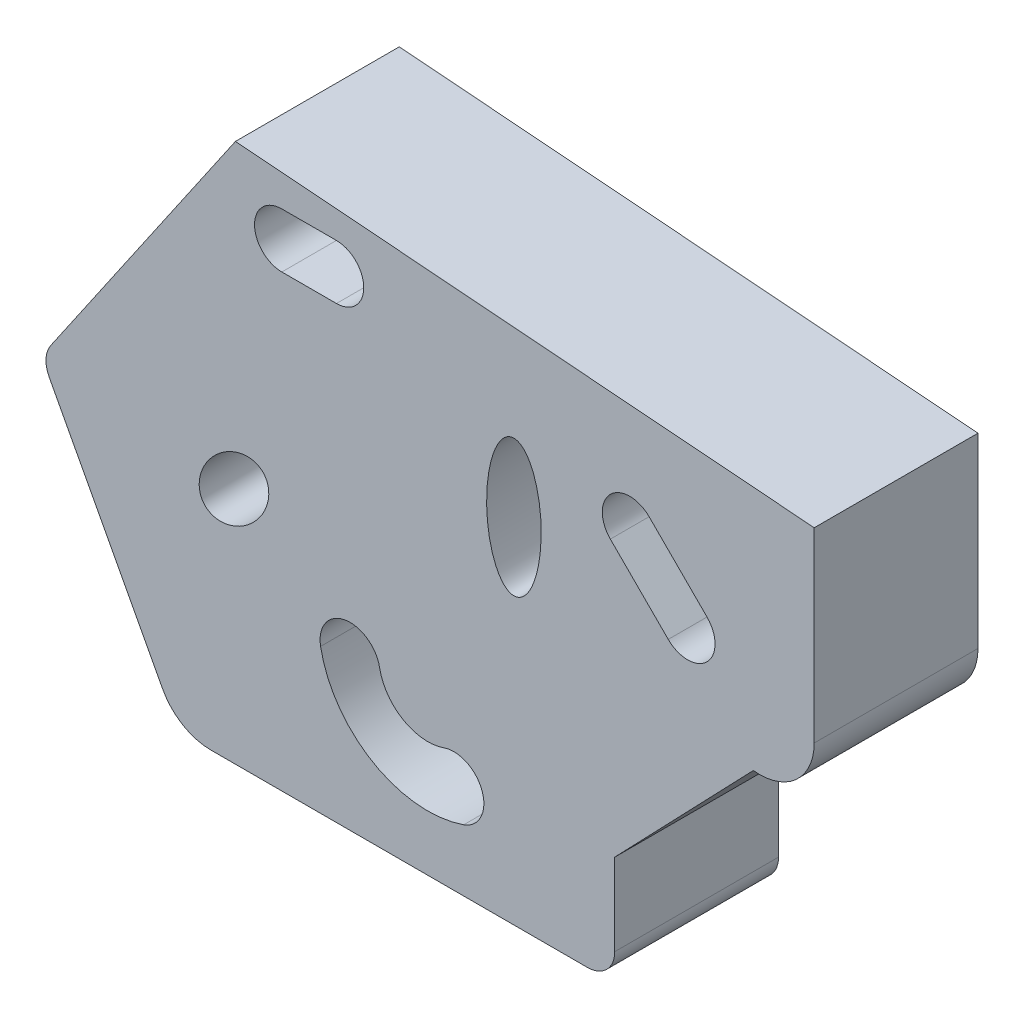
SolidWorks part; units mm, degrees
ref_plane "Front Plane" through (0, 0, 0) normal (0, 0, 1) x (1, 0, 0)
ref_plane "Top Plane" through (0, 0, 0) normal (0, 1, 0) x (1, 0, 0)
ref_plane "Right Plane" through (0, 0, 0) normal (1, 0, 0) x (0, 0, -1)
sketch "草图3" plane through (0, 0, 0) normal (0, 0, 1) x (1, 0, 0)
  line L0 (0, 0) -> (212, -16.5598)
  line L1 (212, -16.5598) -> (212, -84.8498)
  line L2 (189.6995, -104.717) -> (138.9354, -157.5794)
  line L3 (138.9354, -157.5794) -> (138.9354, -187.5794)
  line L4 (128.9354, -197.5794) -> (-9.0474, -197.5794)
  line L5 (-26.7064, -186.9688) -> (-68.2217, -108.8898)
  line L6 (-67.6368, -98.5358) -> (0, 0)
  line L7 (102, -7.9674) -> (102, -197.5794) construction
  line L8 (17, -22.9206) -> (37, -22.9206) construction
  line L9 (17, -12.9206) -> (37, -12.9206)
  line L10 (17, -32.9206) -> (37, -32.9206)
  line L11 (102, -7.9674) -> (-44.1655, -154.1329) construction
  line L12 (102, -7.9674) -> (194.1329, -100.1003) construction
  line L13 (144.4264, -50.3938) -> (165.6396, -71.6071) construction
  line L14 (151.5275, -43.2927) -> (172.7407, -64.5059)
  line L15 (137.3253, -57.495) -> (158.5385, -78.7082)
  arc A0 (212, -84.8498) -> (189.6995, -104.717) centre (192, -84.8498) cw
  arc A1 (128.9354, -197.5794) -> (138.9354, -187.5794) centre (128.9354, -187.5794) ccw
  arc A2 (-9.0474, -197.5794) -> (-26.7064, -186.9688) centre (-9.0474, -177.5794) cw
  arc A3 (-68.2217, -108.8898) -> (-67.6368, -98.5358) centre (-59.3922, -104.1951) cw
  arc A4 (17, -12.9206) -> (17, -32.9206) centre (17, -22.9206) ccw
  arc A5 (37, -32.9206) -> (37, -12.9206) centre (37, -22.9206) ccw
  arc A6 (151.5275, -43.2927) -> (137.3253, -57.495) centre (144.4264, -50.3938) ccw
  arc A7 (158.5385, -78.7082) -> (172.7407, -64.5059) centre (165.6396, -71.6071) ccw
  arc A8 (42, -142.5794) -> (80, -164.5794) centre (70.4571, -137.2444) ccw construction
  arc A13 (31.1884, -144.6063) -> (83.6256, -174.9647) centre (70.4571, -137.2444) ccw
  arc A14 (52.8116, -140.5525) -> (76.3744, -154.1941) centre (70.4571, -137.2444) ccw
  arc A15 (52.8116, -140.5525) -> (31.1884, -144.6063) centre (42, -142.5794) ccw
  arc A16 (83.6256, -174.9647) -> (76.3744, -154.1941) centre (80, -164.5794) ccw
  ellipse E0 centre (-0.5305, -110.4979) end of major axis (-11.1371, -121.1045) minor radius 10
  ellipse E1 centre (102, -68.1502) end of major axis (102, -43.1502) minor radius 10
  point P16 (27, -22.9206)
  point P21 (-21.0646, -197.5794)
  point P42 (155.033, -61.0004)
  point P50 (55.9507, -162.301)
  point P57 (-121.0684, 9.2337)
  point P58 (42.0768, -128.1805)
  point P59 (-138.5387, -38.1052)
  dimension "D4" = 20
  dimension "D7" = 20
  dimension "D11" = 20
  dimension "D12" = 10
  dimension "D16" = 118
  dimension "D18" = 20
  dimension "D35" = 11
  dimension "D1" = 102
  dimension "D2" = 110
  dimension "D3" = 68.29
  dimension "D5" = 136.16
  dimension "D6" = 73.29
  dimension "D8" = 30
  dimension "D9" = 136.16
  dimension "D10" = 150
  dimension "D13" = 88.43
  dimension "D14" = 119.5159
  dimension "D15" = 120
  dimension "D17" = 40
  dimension "D19" = 10
  dimension "D20" = 65
  dimension "D21" = 90
  dimension "D22" = 45
  dimension "D23" = 30
  dimension "D24" = 20
  dimension "D25" = 145
  dimension "D26" = 20
  dimension "D27" = 60
  dimension "D28" = 30
  dimension "D29" = 60
  dimension "D30" = 20.085
  dimension "D31" = 60
  dimension "D32" = 55
  dimension "D33" = 22
  dimension "D34" = 33
  dimension "D36" = 50
extrude "凸台-拉伸1" add sketch "草图3" along normal blind 10 contours A3 L5 A2 L4 A1 L3 L2 A0 L1 L0 L6 | L10 A5 L9 A4 | E1 | L15 A7 L14 A6 | A14 A16 A13 A15 | E0
extrude "凸台-拉伸2" add sketch "草图3<3>" along normal blind 60
sketch "草图3<3>" plane through (0, 0, 0) normal (0, 0, 1) x (1, 0, 0) same geometry as "草图3"
